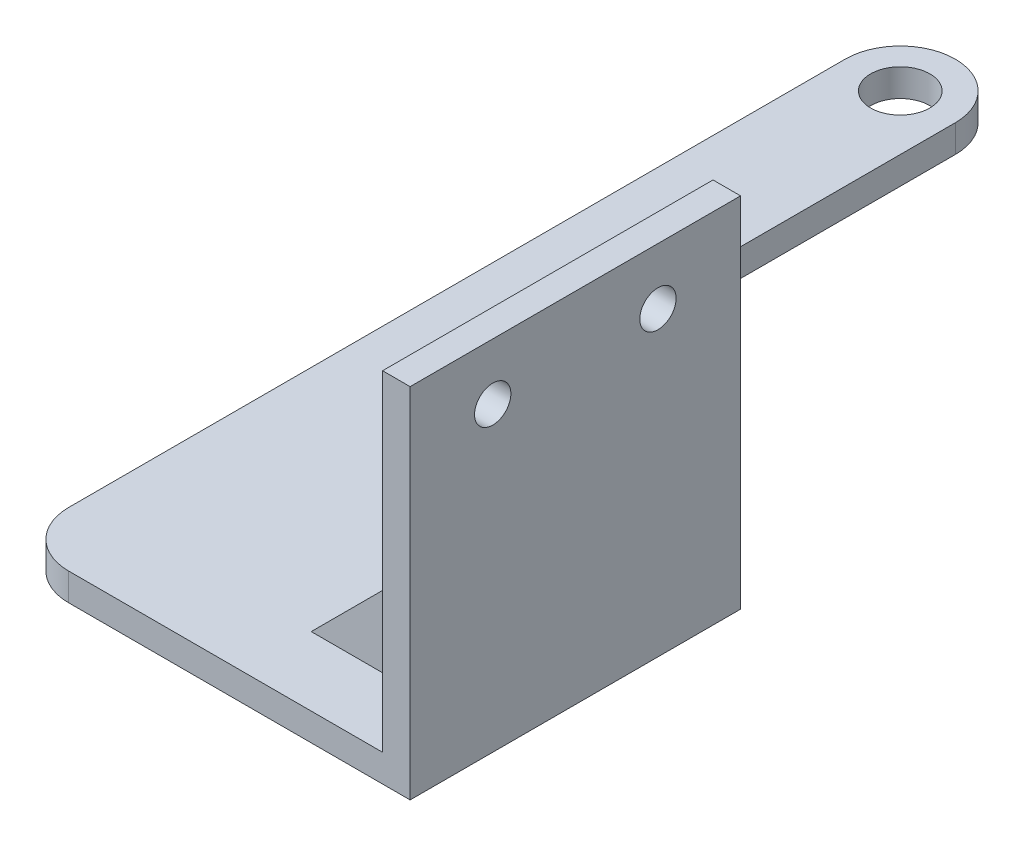
SolidWorks part; units mm, degrees
ref_plane "Front Plane" through (0, 0, 0) normal (0, 0, 1) x (1, 0, 0)
ref_plane "Top Plane" through (0, 0, 0) normal (0, 1, 0) x (1, 0, 0)
ref_plane "Right Plane" through (0, 0, 0) normal (1, 0, 0) x (0, 0, -1)
sketch "Sketch1" plane through (0, 0, 0) normal (0, 0, 1) x (1, 0, 0)
  line L0 (-5, 0) -> (-5, -50)
  line L1 (-5, -50) -> (-5, -65)
  line L4 (-5, -65) -> (0, -65)
  line L11 (0, -65) -> (0, 0)
  line L12 (0, 0) -> (-5, 0)
  dimension "D2" = 65
  dimension "D11" = 5
  dimension "D12" = 50
extrude "Boss-Extrude1" add sketch "Sketch1" along normal blind 60
sketch "Sketch3" plane through (-5, 0, 0) normal (-1, 0, 0) x (0, 0, 1)
  line L0 (0, 0) -> (0, -65) construction
  line L1 (0, -60) -> (60, -60)
  line L2 (0, -60) -> (0, -65)
  line L3 (0, -65) -> (60, -65)
  line L4 (60, -60) -> (60, -65)
  dimension "D1" = 5
extrude "Boss-Extrude2" add sketch "Sketch3" along normal blind 67
sketch "Sketch4" plane through (0, 0, 0) normal (0, 0, -1) x (-1, 0, 0)
  line L1 (52, -60) -> (72, -60)
  line L2 (52, -60) -> (52, -65)
  line L3 (52, -65) -> (72, -65)
  line L4 (72, -60) -> (72, -65)
  line L5 (72, -60) -> (5, -60) construction
  dimension "D1" = 20
extrude "Boss-Extrude3" add sketch "Sketch4" along normal blind 101 contours L2 L1 L4 L3
sketch "Sketch6" plane through (0, -60, 0) normal (0, 1, 0) x (1, 0, 0)
  line L0 (-62, 101) -> (-62, 45.0073) construction
  line L1 (-52, 101) -> (-72, 101) construction
  circle A0 centre (-62, 91) radius 5.375
  dimension "D1" = 10.75
  dimension "D2" = 10
extrude "Cut-Extrude1" cut sketch "Sketch6" against normal up to next
sketch "Sketch11" plane through (-5, 0, 0) normal (-1, 0, 0) x (0, 0, 1)
  line L0 (-19.8478, -10.25) -> (79.4829, -10.25) construction
  line L1 (60, 0) -> (0, 0) construction
  line L2 (8.125, -10.25) -> (21.875, -10.25) construction
  line L3 (8.125, -4.625) -> (21.875, -4.625) construction
  line L4 (8.125, -15.875) -> (21.875, -15.875) construction
  line L5 (38.125, -10.25) -> (51.875, -10.25) construction
  line L6 (38.125, -4.625) -> (51.875, -4.625) construction
  line L7 (38.125, -15.875) -> (51.875, -15.875) construction
  line L8 (0, 0) -> (0, -60) construction
  circle A0 centre (15, -10.25) radius 3.3
  circle A1 centre (45, -10.25) radius 3.3
  arc A2 (8.125, -4.625) -> (8.125, -15.875) centre (8.125, -10.25) ccw construction
  arc A3 (21.875, -15.875) -> (21.875, -4.625) centre (21.875, -10.25) ccw construction
  arc A4 (38.125, -4.625) -> (38.125, -15.875) centre (38.125, -10.25) ccw construction
  arc A5 (51.875, -15.875) -> (51.875, -4.625) centre (51.875, -10.25) ccw construction
  point P8 (15, -10.25)
  point P15 (45, -10.25)
  dimension "D2" = 6.6
  dimension "D3" = 30
  dimension "D4" = 25
  dimension "D1" = 10.25
  dimension "D5" = 15
  dimension "D6" = 11.25
extrude "Cut-Extrude2" cut sketch "Sketch11" against normal up to next contours A1 | A0
ref_plane "Plane1" through (0, -62.5, 0) normal (0, 1, 0) x (1, 0, 0)
sketch "Sketch12" plane through (0, -62.5, 0) normal (0, 1, 0) x (1, 0, 0)
  line L0 (-62, 82) -> (-62, 101) construction
  line L1 (-52, 101) -> (-64.5, 101)
  line L2 (-52, 101) -> (-52, 82)
  line L3 (-52, 82) -> (-62, 82)
  line L4 (-64.5, 101) -> (-64.5, 99.6458)
  line L5 (-52, 101) -> (-52, 0) construction
  line L7 (-52, 101) -> (-72, 101) construction
  line L9 (-62, 93.5) -> (-62, 88.5) construction
  circle A0 centre (-62, 91) radius 6.5
  circle A1 centre (-62, 91) radius 5.375 construction
  arc A2 (-64.5, 99.6458) -> (-62, 82) centre (-62, 91) ccw
  point P22 (-62, 91)
  dimension "D1" = 13
  dimension "D2" = 18
  dimension "D3" = 5
  dimension "D4" = 2.5
extrude "Cut-Extrude3" [suppressed] cut sketch "Sketch12" against normal blind 2.5 and the other way blind 2.5
fillet "Fillet1" radius 10 2 edges at (-52, -62.5, -101) (-72, -62.5, -101)
fillet "Fillet3" radius 10 1 edges at (-52, -62.5, 0)
fillet "Fillet4" radius 10 1 edges at (-72, -62.5, 60)
ref_plane "Plane2" through (0, 0, 45) normal (0, 0, 1) x (1, 0, 0)
sketch "Sketch13" plane through (0, 0, 45) normal (0, 0, 1) x (1, 0, 0)
  line L0 (-30.4558, -60) -> (-5, -34.5442)
  line L1 (-5, 0) -> (-5, -60) construction
  line L2 (-30.4558, -60) -> (-5, -60)
  line L3 (-62, -60) -> (-5, -60) construction
  line L5 (-5, -60) -> (-5, -34.5442)
  dimension "D1" = 36
extrude "Boss-Extrude4" add sketch "Sketch13" against normal mid plane 5
ref_plane "Plane3" through (0, 0, 30) normal (0, 0, 1) x (1, 0, 0)
mirror "Mirror1" about plane through (0, 0, 30) normal (0, 0, 1) of "Boss-Extrude4"
